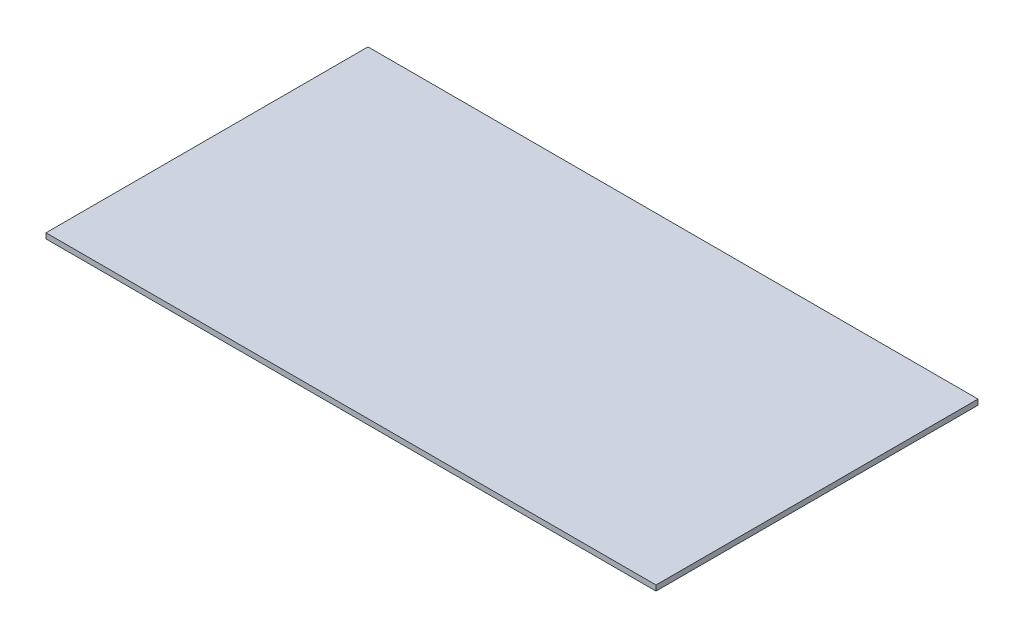
SolidWorks part; units mm, degrees
material "5052-H34"
ref_plane "Front Plane" through (0, 0, 0) normal (0, 0, 1) x (1, 0, 0)
ref_plane "Top Plane" through (0, 0, 0) normal (0, 1, 0) x (1, 0, 0)
ref_plane "Right Plane" through (0, 0, 0) normal (1, 0, 0) x (0, 0, -1)
sketch "Sketch1" plane through (0, 0, 0) normal (0, 0, 1) x (1, 0, 0)
  line L0 (-580.595, 4.4417) -> (-36.865, 4.4417)
  line L1 (-36.865, 4.4417) -> (-36.865, -0.3208)
  line L3 (-36.865, -0.3208) -> (-580.595, -0.3208)
  line L6 (-580.595, 4.4417) -> (-580.595, -0.3208)
  point P2 (-580.595, 4.4417)
extrude "Boss-Extrude1" add sketch "Sketch1" along normal blind 287
sketch "GasketGroove" plane through (0, -0.3208, 0) normal (0, -1, 0) x (1, 0, 0)
  line L0 (-577.595, 283) -> (-577.595, 4)
  line L1 (-576.595, 3) -> (-40.865, 3)
  line L2 (-39.865, 4) -> (-39.865, 283)
  line L3 (-40.865, 284) -> (-576.595, 284)
  line L4 (-579.595, 286) -> (-579.595, 1) construction
  line L5 (-577.595, 286) -> (-577.595, 1) construction
  line L6 (-37.865, 284) -> (-579.595, 284) construction
  line L7 (-579.595, 3) -> (-37.865, 3) construction
  line L8 (-39.865, 1) -> (-39.865, 286) construction
  line L9 (-579.595, 1) -> (-37.865, 1) construction
  line L10 (-37.865, 286) -> (-579.595, 286) construction
  line L11 (-37.865, 1) -> (-37.865, 286) construction
  line L14 (-37.865, 1) -> (-37.865, 286)
  line L15 (-579.595, 1) -> (-37.865, 1)
  line L16 (-579.595, 286) -> (-579.595, 1)
  line L17 (-37.865, 286) -> (-579.595, 286)
  line L18 (-37.865, 2) -> (-37.865, 285)
  line L19 (-578.595, 1) -> (-38.865, 1)
  line L20 (-579.595, 285) -> (-579.595, 2)
  line L21 (-38.865, 286) -> (-578.595, 286)
  arc A0 (-579.595, 2) -> (-578.595, 1) centre (-578.595, 2) ccw
  arc A1 (-579.595, 285) -> (-578.595, 286) centre (-578.595, 285) cw
  arc A2 (-37.865, 285) -> (-38.865, 286) centre (-38.865, 285) ccw
  arc A3 (-38.865, 1) -> (-37.865, 2) centre (-38.865, 2) ccw
  arc A4 (-40.865, 3) -> (-39.865, 4) centre (-40.865, 4) ccw
  arc A5 (-576.595, 3) -> (-577.595, 4) centre (-576.595, 4) cw
  arc A6 (-576.595, 284) -> (-577.595, 283) centre (-576.595, 283) ccw
  arc A7 (-39.865, 283) -> (-40.865, 284) centre (-40.865, 283) ccw
  dimension "D6" = 1
  dimension "D7" = 1
  dimension "D8" = 1
  dimension "D9" = 1
  dimension "D10" = 1
  dimension "D11" = 1
  dimension "D12" = 1
  dimension "D13" = 1
  dimension "D1" = 1
  dimension "D2" = 2
  dimension "D3" = 2
  dimension "D4" = 2
  dimension "D5" = 2
extrude "Cut-Extrude1" cut sketch "GasketGroove" against normal blind 2
